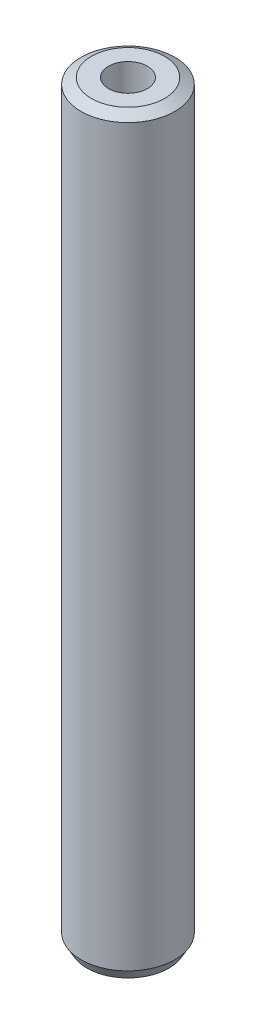
SolidWorks part; units mm, degrees
ref_plane "Front Plane" through (0, 0, 0) normal (0, 0, 1) x (1, 0, 0)
ref_plane "Top Plane" through (0, 0, 0) normal (0, 1, 0) x (1, 0, 0)
ref_plane "Right Plane" through (0, 0, 0) normal (1, 0, 0) x (0, 0, -1)
sketch "Sketch1" plane through (0, 0, 0) normal (0, 1, 0) x (1, 0, 0)
  circle A0 centre (0, 0) radius 37.5
  dimension "SHAFT_OD" = 75
extrude "Boss-Extrude1" add sketch "Sketch1" along normal blind 600
sketch "Sketch2" plane through (0, 0, 0) normal (0, 1, 0) x (1, 0, 0)
  circle A0 centre (0, 0) radius 15.5381
  dimension "BORE_D" = 31.0761
extrude "Cut-Extrude1" cut sketch "Sketch2" along normal through all
chamfer "Chamfer1" distance 4.7794 angle 60 2 edges at (0, 600, 37.5) (0, 0, 37.5) first distance on face at (0, 600, 37.5) first distance on face at (0, 0, 15.5381)
